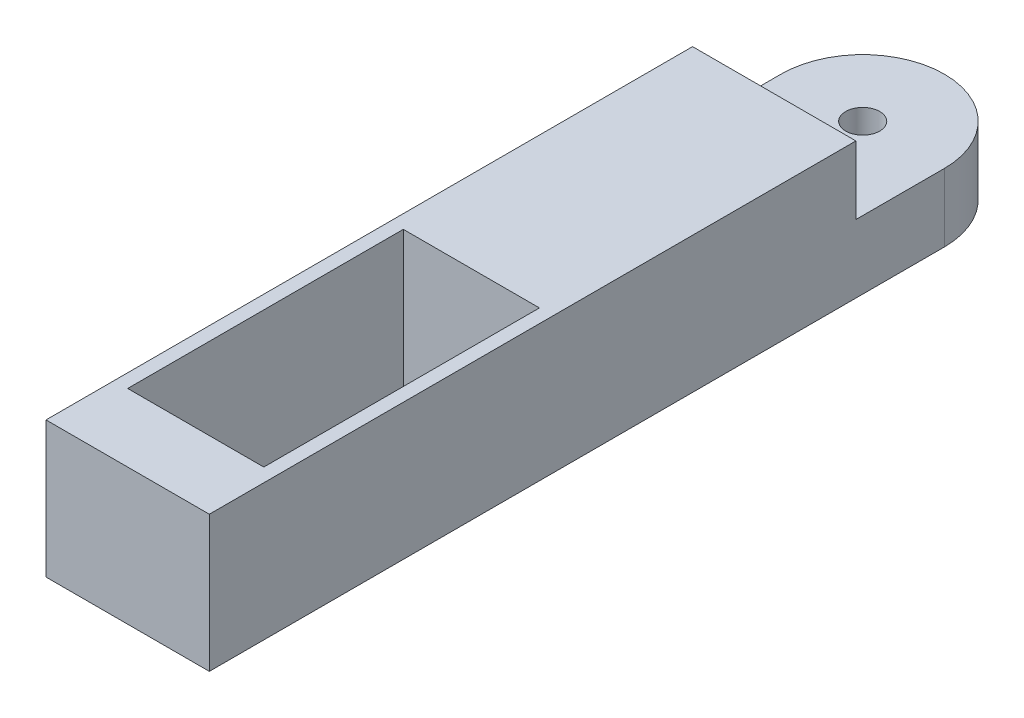
SolidWorks part; units mm, degrees
material "ABS"
ref_plane "Front Plane" through (0, 0, 0) normal (0, 0, 1) x (1, 0, 0)
ref_plane "Top Plane" through (0, 0, 0) normal (0, 1, 0) x (1, 0, 0)
ref_plane "Right Plane" through (0, 0, 0) normal (1, 0, 0) x (0, 0, -1)
sketch "Sketch3" plane through (0, 0, 0) normal (0, 1, 0) x (1, 0, 0)
  line L2 (-20, 20) -> (-20, 7)
  line L3 (-20, 7) -> (4, 7)
  line L4 (4, 20) -> (4, 7)
  arc A0 (4, 20) -> (-20, 20) centre (-8, 20) ccw
  circle A1 centre (-8, 20) radius 2.5
extrude "Boss-Extrude2" add sketch "Sketch3" along normal blind 10 contours A1 | L2 L3 L4 A0 region at (-8, 0, -20)
sketch "Sketch4" plane through (0, 10, 0) normal (0, 1, 0) x (1, 0, 0)
  line L0 (4, 20) -> (4, 7) construction
  line L1 (-20, 7) -> (4, 7)
  line L2 (-20, 7) -> (-20, -88)
  line L3 (-20, -88) -> (4, -88)
  line L4 (4, 7) -> (4, -88)
  line L5 (-18, -78) -> (2, -78)
  line L7 (2, -78) -> (2, -37.5)
  line L8 (2, -37.5) -> (-18, -37.5)
  line L9 (-18, -37.5) -> (-18, -78)
extrude "Boss-Extrude3" add sketch "Sketch4" along normal blind 10 and the other way blind 10
